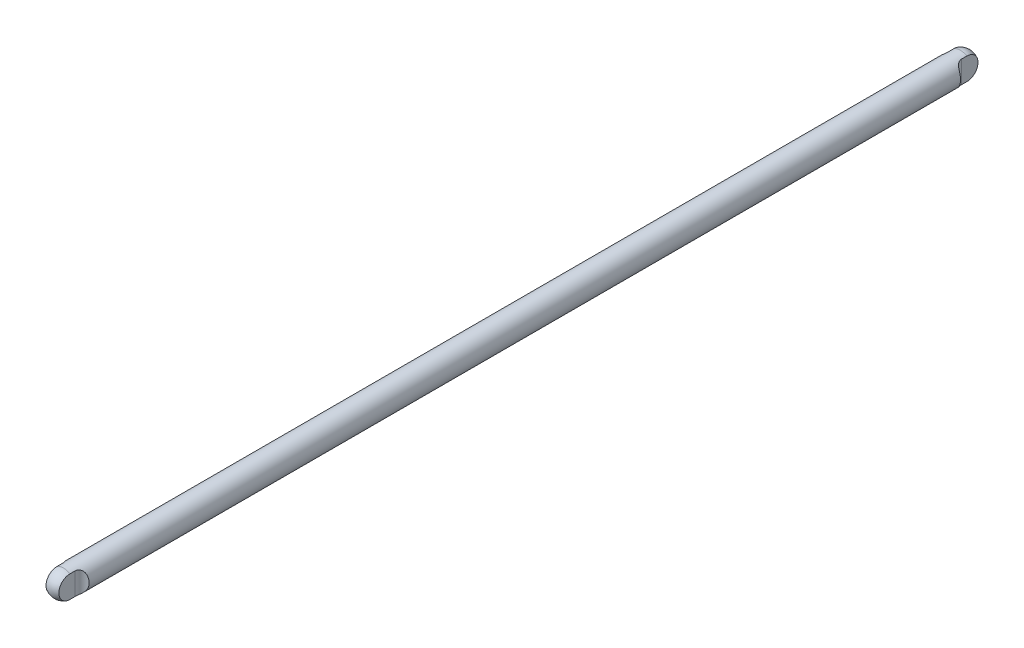
SolidWorks part; units mm, degrees
ref_plane "Piano frontale" through (0, 0, 0) normal (0, 0, 1) x (1, 0, 0)
ref_plane "Piano superiore" through (0, 0, 0) normal (0, 1, 0) x (1, 0, 0)
ref_plane "Piano destro" through (0, 0, 0) normal (1, 0, 0) x (0, 0, -1)
sketch "Schizzo5" plane through (0, 0, 0) normal (0, 0, 1) x (1, 0, 0)
  circle A0 centre (0, 0) radius 5
extrude "Estrusione-Estrusione2" add sketch "Schizzo5" along normal blind 349.1
sketch "Schizzo9" plane through (0, 0, 0) normal (0, 0, -1) x (-1, 0, 0)
  line L0 (5, 0) -> (-5, 0)
  arc A0 (-5, 0) -> (5, 0) centre (0, 0) cw
  circle A1 centre (0, 0) radius 5 construction
revolve "Rivoluzione13" add sketch "Schizzo9" angle 180 about L0 reverse direction yes
sketch "Schizzo10" plane through (0, 0, 0) normal (0, 0, 1) x (1, 0, 0)
  line L0 (2, 0) -> (-2, 0)
  arc A0 (2, 0) -> (-2, 0) centre (0, 0) ccw
revolve "Rivoluzione14" add sketch "Schizzo10" angle 360 about L0
combine bodies "Abbina1" operation type subtract main body 104 bodies to subtract 105
ref_plane "Piano1" through (0, -5, 0) normal (0, -1, 0) x (-1, 0, 0)
sketch "Schizzo11" plane through (0, -5, 0) normal (0, -1, 0) x (-1, 0, 0)
  line L0 (-5, 0) -> (5, 0) construction
  line L1 (2.5, -5) -> (7.5, -5)
  line L2 (2.5, -5) -> (2.5, 10)
  line L3 (2.5, 10) -> (7.5, 10)
  line L4 (7.5, -5) -> (7.5, 10)
  line L5 (5, -349.1) -> (5, 0) construction
  dimension "D1" = 15
  dimension "D2" = 5
  dimension "D3" = 10
  dimension "D4" = 2.5
extrude "Taglio-Estrusione1" cut sketch "Schizzo11" against normal through all contours L4 L3 L2 L1
mirror "Specchia1" about plane through (0, 0, 0) normal (1, 0, 0) of "Taglio-Estrusione1"
fillet "Raccordo1" radius 3 1 edges at (-2.5, 0, 5)
fillet "Raccordo2" radius 3 1 edges at (2.5, 0, 5)
ref_plane "Piano2" through (0, 0, 349.1) normal (0, 0, 1) x (1, 0, 0)
sketch "Schizzo13" plane through (0, 0, 349.1) normal (0, 0, 1) x (1, 0, 0)
  line L0 (0, 5) -> (0, -5)
  arc A0 (0, 5) -> (0, -5) centre (0, 0) ccw
  circle A1 centre (0, 0) radius 5 construction
revolve "Rivoluzione16" add sketch "Schizzo13" angle 180 about L0 reverse direction yes
sketch "Schizzo15" plane through (0, 0, 349.1) normal (0, 0, 1) x (1, 0, 0)
  line L0 (0, -2) -> (0, 2)
  arc A0 (0, 2) -> (0, -2) centre (0, 0) cw
revolve "Rivoluzione18" add sketch "Schizzo15" angle 360 about L0
combine bodies "Abbina2" operation type subtract main body 111 bodies to subtract 113
sketch "Schizzo16" plane through (0, -5, 0) normal (0, -1, 0) x (-1, 0, 0)
  line L1 (-7.5, -359.1) -> (-2.5, -359.1)
  line L2 (-7.5, -359.1) -> (-7.5, -344.1)
  line L3 (-7.5, -344.1) -> (-2.5, -344.1)
  line L4 (-2.5, -359.1) -> (-2.5, -344.1)
  line L5 (-11, -349.1) -> (11, -349.1) construction
  line L6 (-5, -4.958) -> (-5, -349.1) construction
  dimension "D1" = 15
  dimension "D2" = 5
  dimension "D3" = 10
  dimension "D4" = 2.5
extrude "Taglio-Estrusione2" cut sketch "Schizzo16" against normal through all
mirror "Specchia10" about plane through (0, 0, 0) normal (1, 0, 0) of "Taglio-Estrusione2"
fillet "Raccordo3" radius 3 1 edges at (-2.5, 0, 344.1)
fillet "Raccordo4" radius 3 1 edges at (2.5, 0, 344.1)
